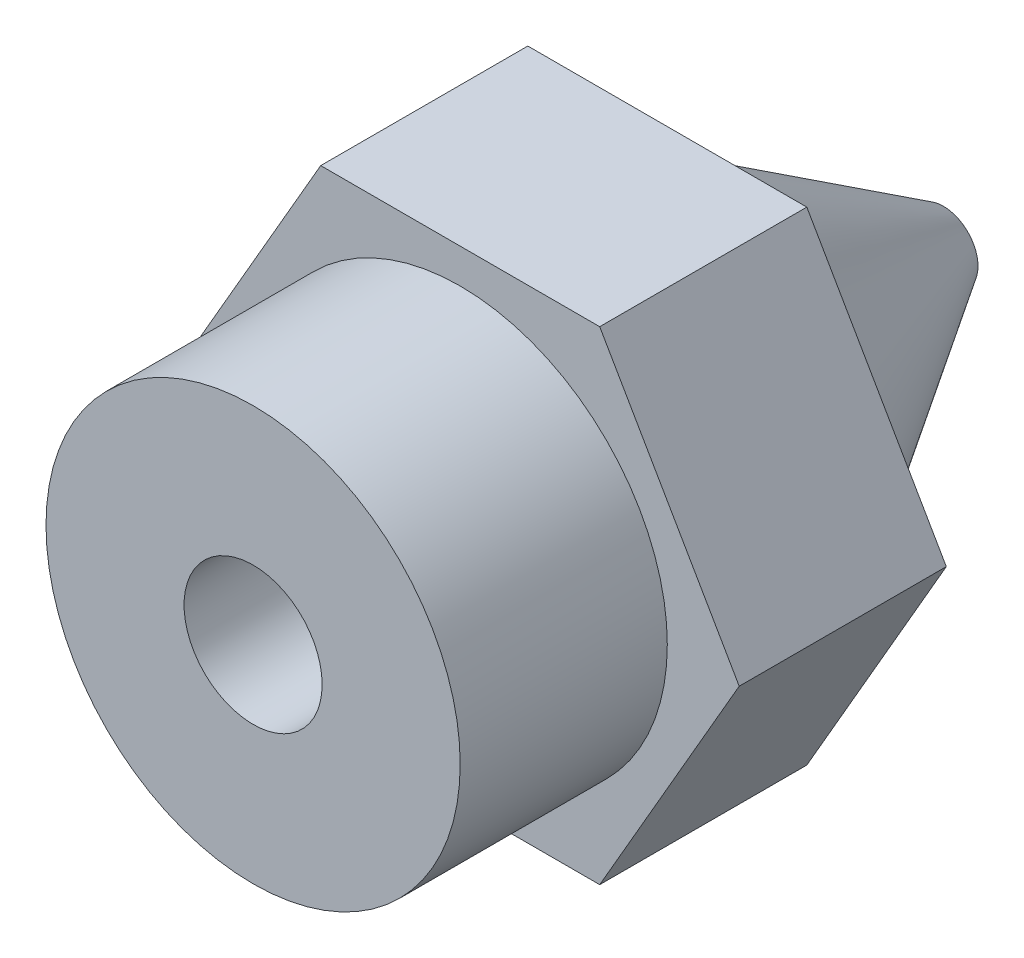
SolidWorks part; units mm, degrees
ref_plane "Plan de face" through (0, 0, 0) normal (0, 0, 1) x (1, 0, 0)
ref_plane "Plan de dessus" through (0, 0, 0) normal (0, 1, 0) x (1, 0, 0)
ref_plane "Plan de droite" through (0, 0, 0) normal (1, 0, 0) x (0, 0, -1)
sketch "Esquisse1" plane through (0, 0, 0) normal (0, 0, 1) x (1, 0, 0)
  line L1 (4.0415, 0) -> (2.0207, 3.5)
  line L2 (2.0207, 3.5) -> (-2.0207, 3.5)
  line L3 (-2.0207, 3.5) -> (-4.0415, 0)
  line L4 (-4.0415, 0) -> (-2.0207, -3.5)
  line L5 (-2.0207, -3.5) -> (2.0207, -3.5)
  line L6 (2.0207, -3.5) -> (4.0415, 0)
  circle A0 centre (0, 0) radius 3.5 construction
  dimension "D1" = 7
extrude "Boss.-Extru.1" add sketch "Esquisse1" along normal blind 10
sketch "Esquisse2" plane through (0, 0, 10) normal (0, 0, 1) x (1, 0, 0)
  line L1 (-7.9912, 5.5023) -> (7.566, 5.5023)
  line L2 (-7.9912, 5.5023) -> (-7.9912, -5.9665)
  line L3 (-7.9912, -5.9665) -> (7.566, -5.9665)
  line L4 (7.566, 5.5023) -> (7.566, -5.9665)
  circle A0 centre (0, 0) radius 3
  dimension "D1" = 6
extrude "Enlèv. mat.-Extru.1" cut sketch "Esquisse2" against normal blind 3
cosmetic thread "Représentation de filetage1" parameters "D2"=4.891
sketch "Esquisse3" plane through (0, 0, 0) normal (0, 0, -1) x (-1, 0, 0)
  line L1 (7.8656, -6.0768) -> (-7.4574, -6.0768)
  line L2 (7.8656, -6.0768) -> (7.8656, 5.7844)
  line L3 (7.8656, 5.7844) -> (-7.4574, 5.7844)
  line L4 (-7.4574, -6.0768) -> (-7.4574, 5.7844)
  circle A0 centre (0, 0) radius 3
  dimension "D1" = 6
extrude "Enlèv. mat.-Extru.3" cut sketch "Esquisse3" against normal blind 4
chamfer "Chanfrein2" distance 4 angle 32 1 edges at (-3, 0, 0) first distance on face at (-3, 0, 4)
sketch "Esquisse4" plane through (0, 0, 0) normal (0, 1, 0) x (1, 0, 0)
  line L0 (0, 0) -> (0, -10) construction
  line L1 (0.5005, 0) -> (-0.5005, 0) construction
  line L2 (-3, -10) -> (3, -10) construction
  line L3 (0, 0) -> (0.2, 0) construction
  line L4 (0, 1.4) -> (1, -5.6) construction
  line L5 (0, 0) -> (0, 1.4) construction
  line L6 (0.2, 0) -> (0.2, -1.4) construction
  line L7 (0.2, -1.4) -> (0, -1.4) construction
  line L8 (0, 1.4) -> (1, -5.6)
  line L9 (1, -5.6) -> (1, -10)
  line L10 (1, -10) -> (0, -10)
  line L11 (0, -10) -> (0, 1.4)
  dimension "D1" = 7
  dimension "D2" = 1
revolve "Enlèvement de matière-Révolution1" cut sketch "Esquisse4" angle 360 about L11
